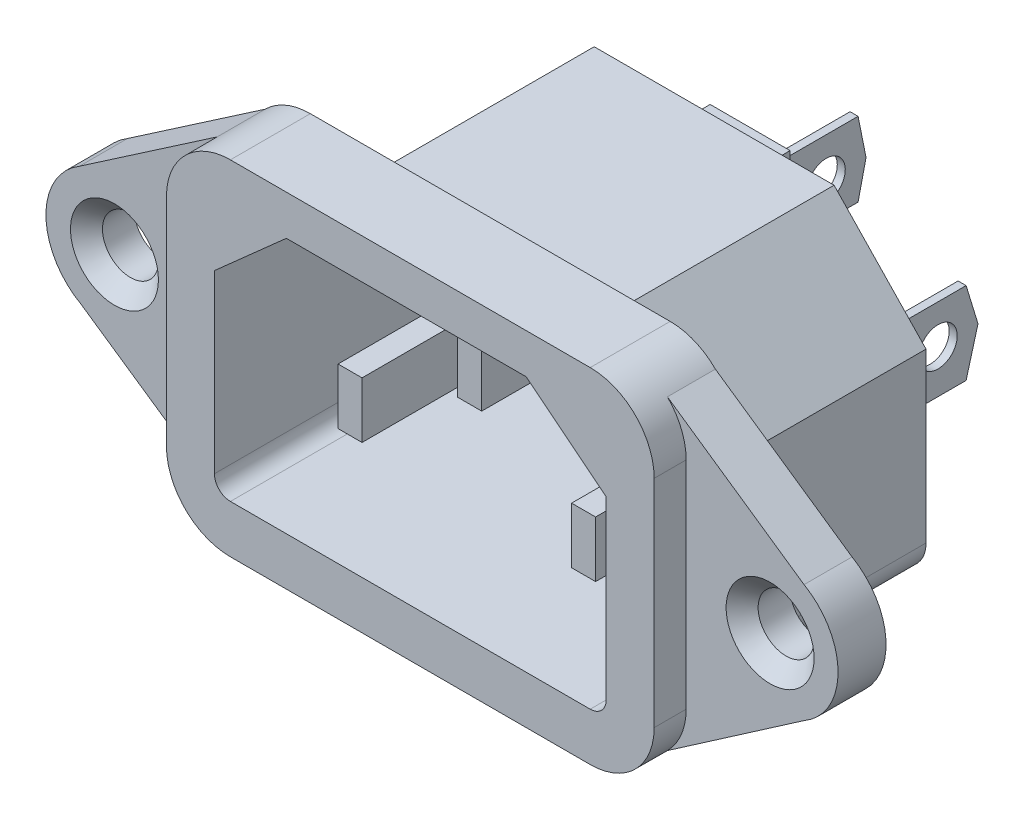
SolidWorks part; units mm, degrees
ref_plane "Спереди" through (0, 0, 0) normal (0, 0, 1) x (1, 0, 0)
ref_plane "Сверху" through (0, 0, 0) normal (0, 1, 0) x (1, 0, 0)
ref_plane "Справа" through (0, 0, 0) normal (1, 0, 0) x (0, 0, -1)
sketch "Эскиз1" plane through (0, 0, 0) normal (0, 0, 1) x (1, 0, 0)
  line L0 (23.0556, -0.5833) -> (-26.4444, -0.5833) construction
  line L1 (-12.9444, 10.1667) -> (9.5556, 10.1667)
  line L2 (-16.9444, 6.1667) -> (-16.9444, -7.3333)
  line L3 (-12.9444, -11.3333) -> (9.5556, -11.3333)
  line L4 (13.5556, 6.1667) -> (13.5556, -7.3333)
  line L5 (-15.7729, 8.9951) -> (-24.3879, 3.0982)
  line L6 (-24.2767, -4.329) -> (-15.7729, -10.1618)
  line L7 (12.384, 8.9951) -> (20.9289, 3.0982)
  line L8 (20.9289, -4.2649) -> (12.384, -10.1618)
  arc A0 (-12.9444, 10.1667) -> (-16.9444, 6.1667) centre (-12.9444, 6.1667) ccw
  arc A1 (-16.9444, -7.3333) -> (-12.9444, -11.3333) centre (-12.9444, -7.3333) ccw
  arc A2 (9.5556, -11.3333) -> (13.5556, -7.3333) centre (9.5556, -7.3333) ccw
  arc A3 (9.5556, 10.1667) -> (13.5556, 6.1667) centre (9.5556, 6.1667) cw
  circle A5 centre (-22.1944, -0.5833) radius 1.75
  circle A6 centre (18.8056, -0.5833) radius 1.75
  arc A7 (20.9289, -4.2649) -> (20.9289, 3.0982) centre (18.8056, -0.5833) ccw
  arc A8 (-24.3879, 3.0982) -> (-24.2767, -4.329) centre (-22.1944, -0.5833) ccw
  point P6 (-16.9444, 10.1667)
  point P11 (13.5556, -11.3333)
  point P14 (13.5556, 10.1667)
  point P21 (-16.9444, -0.5833)
  dimension "D3" = 4
  dimension "D5" = 4.25
  dimension "D6" = 4.25
  dimension "D1" = 30.5
  dimension "D2" = 21.5
  dimension "D4" = 9.5
  dimension "D7" = 5.25
  dimension "D8" = 5.25
extrude "Бобышка-Вытянуть1" add sketch "Эскиз1" against normal blind 3 contours L4 L0 L2 A1 L3 A2 | L0 L4 A3 L1 A0 L2 | A7 L0 A6 L4 A2 L8 | L0 A7 L7 A3 L4 A6 | L5 A8 L6 A1 L2 A5 A0 region at (17.0838, -3.9737, 0) region at (17.0838, 2.8071, 0) region at (-1.6944, -5.8625, 0) region at (-1.6944, 4.6958, 0) region at (-17.1639, -3.9583, 0)
sketch "Эскиз3" plane through (0, 0, 0) normal (0, 0, 1) x (1, 0, 0)
  line L0 (-12.9444, 10.1667) -> (9.5556, 10.1667) construction
  line L1 (-12.9444, 10.1667) -> (9.5556, 10.1667)
  line L2 (-16.9444, 6.1667) -> (-16.9444, -7.3333)
  line L3 (-12.9444, -11.3333) -> (9.5556, -11.3333)
  line L4 (13.5556, 6.1667) -> (13.5556, -7.3333)
  arc A0 (9.5556, 10.1667) -> (13.5556, 6.1667) centre (9.5556, 6.1667) cw
  arc A1 (9.5556, -11.3333) -> (13.5556, -7.3333) centre (9.5556, -7.3333) ccw
  arc A2 (-16.9444, -7.3333) -> (-12.9444, -11.3333) centre (-12.9444, -7.3333) ccw
  arc A3 (-12.9444, 10.1667) -> (-16.9444, 6.1667) centre (-12.9444, 6.1667) ccw
  point P4 (-1.6944, 10.1667)
  point P7 (-1.6944, 10.1667)
  point P10 (13.5556, 10.1667)
  point P15 (-16.9444, -11.3333)
  point P18 (-16.9444, 10.1667)
  dimension "D3" = 4
  dimension "D1" = 30.5
  dimension "D2" = 21.5
extrude "Бобышка-Вытянуть2" add sketch "Эскиз3" along normal blind 2
sketch "Эскиз4" plane through (0, 0, -3) normal (0, 0, -1) x (-1, 0, 0)
  line L0 (1.7119, 8.6668) -> (1.7119, -9.8333) construction
  line L1 (-5.8056, 8.6667) -> (9.1944, 8.6667)
  line L2 (-11.5556, 2.6667) -> (-11.5556, -7.8333)
  line L3 (-9.5556, -9.8333) -> (12.9795, -9.8333)
  line L4 (14.9795, 2.6667) -> (14.9795, -7.8333)
  line L5 (12.9444, 10.1667) -> (-9.5556, 10.1667) construction
  line L6 (12.9444, -11.3333) -> (-9.5556, -11.3333) construction
  line L7 (-11.2855, 2.6667) -> (-11.5556, 2.6667) construction
  line L11 (-11.5556, 2.6667) -> (-5.8056, 8.6667)
  line L12 (9.1944, 8.6667) -> (14.9795, 2.6667)
  arc A0 (-20.9289, 3.0982) -> (-20.9289, -4.2649) centre (-18.8056, -0.5833) ccw construction
  arc A1 (24.2767, -4.329) -> (24.3879, 3.0982) centre (22.1944, -0.5833) ccw construction
  arc A2 (-11.5556, -7.8333) -> (-9.5556, -9.8333) centre (-9.5556, -7.8333) ccw
  arc A3 (12.9795, -9.8333) -> (14.9795, -7.8333) centre (12.9795, -7.8333) ccw
  point P9 (-23.0556, -0.5833)
  point P12 (1.6944, 10.1667)
  point P17 (26.4795, -0.6475)
  point P19 (1.7119, 6.1202)
  dimension "D5" = 2
  dimension "D1" = 11.5
  dimension "D2" = 11.5
  dimension "D3" = 1.5
  dimension "D4" = 1.5
extrude "Бобышка-Вытянуть3" add sketch "Эскиз4" along normal blind 14
sketch "Эскиз5" plane through (0, 0, -3) normal (0, 0, -1) x (-1, 0, 0)
  line L0 (-17.1431, 3.368) -> (-10.047, 8.2024)
  line L1 (-10.047, 8.2024) -> (-8.1409, 8.2024)
  line L2 (-8.1409, 8.2024) -> (-13.1129, 2.8675)
  line L3 (-13.1129, 2.8675) -> (-13.1129, -7.3555)
  line L4 (-13.1129, -7.3555) -> (-17.1431, -4.5346)
  line L5 (20.5354, 3.368) -> (13.5142, 8.2024)
  line L6 (13.5142, 8.2024) -> (11.5035, 8.2024)
  line L7 (11.5035, 8.2024) -> (16.8383, 2.8675)
  line L8 (16.8383, 2.8675) -> (16.8383, -7.0285)
  line L9 (16.8383, -7.0285) -> (20.5354, -4.5346)
  arc A0 (-17.1431, -4.5346) -> (-17.1431, 3.368) centre (-18.8056, -0.5833) ccw
  arc A1 (20.5354, 3.368) -> (20.5354, -4.5346) centre (22.1944, -0.5833) ccw
extrude "Вырез-Вытянуть1" cut sketch "Эскиз5" against normal blind 1
chamfer "Фаска1" distance 1 angle 45 1 edges at (20.5556, -0.5833, 0)
chamfer "Фаска2" distance 1 angle 45 1 edges at (-20.4444, -0.5833, 0)
sketch "Эскиз6" plane through (0, 0, -17) normal (0, 0, -1) x (-1, 0, 0)
  line L0 (9.1944, 8.6667) -> (-5.8056, 8.6667) construction
  line L1 (-8.0556, 1.6667) -> (-3.0556, 1.6667)
  line L2 (-8.0556, 1.6667) -> (-8.0556, -8.3333)
  line L3 (-8.0556, -8.3333) -> (-3.0556, -8.3333)
  line L4 (-3.0556, 1.6667) -> (-3.0556, -8.3333)
  line L5 (-8.0556, 1.6667) -> (-3.0556, -8.3333) construction
  line L6 (-8.0556, -8.3333) -> (-3.0556, 1.6667) construction
  line L7 (-1.0556, 7.1667) -> (3.9444, 7.1667)
  line L8 (-1.0556, 7.1667) -> (-1.0556, -2.8333)
  line L9 (-1.0556, -2.8333) -> (3.9444, -2.8333)
  line L10 (3.9444, 7.1667) -> (3.9444, -2.8333)
  line L11 (-1.0556, 7.1667) -> (3.9444, -2.8333) construction
  line L12 (-1.0556, -2.8333) -> (3.9444, 7.1667) construction
  line L13 (6.4795, 1.6667) -> (11.4795, 1.6667)
  line L14 (6.4795, 1.6667) -> (6.4795, -8.3333)
  line L15 (6.4795, -8.3333) -> (11.4795, -8.3333)
  line L16 (11.4795, 1.6667) -> (11.4795, -8.3333)
  line L17 (6.4795, 1.6667) -> (11.4795, -8.3333) construction
  line L18 (6.4795, -8.3333) -> (11.4795, 1.6667) construction
  line L19 (9.1944, 8.6667) -> (-5.8056, 8.6667) construction
  line L20 (-11.5556, 2.6667) -> (-11.5556, -7.8333) construction
  line L21 (14.9795, -7.8333) -> (14.9795, 2.6667) construction
  line L22 (-9.5556, -9.8333) -> (12.9795, -9.8333) construction
  line L23 (-11.5556, 2.6667) -> (-11.5556, -7.8333) construction
  point P0 (-5.5556, -3.3333)
  point P5 (1.4444, 2.1667)
  point P10 (8.9795, -3.3333)
  dimension "D1" = 5
  dimension "D2" = 10
  dimension "D3" = 5
  dimension "D4" = 10
  dimension "D5" = 5
  dimension "D6" = 10
  dimension "D7" = 7
  dimension "D8" = 7
  dimension "D9" = 3.5
  dimension "D10" = 3.5
  dimension "D11" = 7
  dimension "D12" = 10.5
extrude "Бобышка-Вытянуть4" add sketch "Эскиз6" along normal blind 2
sketch "Эскиз7" plane through (0, 0, -19) normal (0, 0, -1) x (-1, 0, 0)
  line L0 (-8.0556, -8.3333) -> (-3.0556, -8.3333) construction
  line L1 (-5.8056, 0.6667) -> (-5.3056, 0.6667)
  line L2 (-5.8056, 0.6667) -> (-5.8056, -7.3333)
  line L3 (-5.8056, -7.3333) -> (-5.3056, -7.3333)
  line L4 (-5.3056, 0.6667) -> (-5.3056, -7.3333)
  line L5 (-8.0556, 1.6667) -> (-8.0556, -8.3333) construction
  line L7 (11.4795, -8.3333) -> (11.4795, 1.6667) construction
  line L8 (1.1944, 6.1667) -> (1.6944, 6.1667)
  line L9 (1.1944, 6.1667) -> (1.1944, -1.8333)
  line L10 (1.1944, -1.8333) -> (1.6944, -1.8333)
  line L11 (1.6944, 6.1667) -> (1.6944, -1.8333)
  line L12 (8.7295, 0.6667) -> (9.2295, 0.6667)
  line L13 (8.7295, 0.6667) -> (8.7295, -7.3333)
  line L14 (8.7295, -7.3333) -> (9.2295, -7.3333)
  line L15 (9.2295, 0.6667) -> (9.2295, -7.3333)
  line L16 (3.9444, -2.8333) -> (3.9444, 7.1667) construction
  line L17 (-1.0556, -2.8333) -> (3.9444, -2.8333) construction
  line L18 (6.4795, -8.3333) -> (11.4795, -8.3333) construction
  dimension "D1" = 0.5
  dimension "D2" = 8
  dimension "D3" = 1
  dimension "D4" = 2.25
  dimension "D5" = 0.5
  dimension "D6" = 8
  dimension "D7" = 0.5
  dimension "D8" = 8
  dimension "D9" = 2.25
  dimension "D10" = 2.25
  dimension "D11" = 1
  dimension "D12" = 1
extrude "Бобышка-Вытянуть5" add sketch "Эскиз7" along normal mid plane 14
sketch "Эскиз8" plane through (-9.2295, 0, 0) normal (-1, 0, 0) x (0, 0, 1)
  line L0 (-26, -3.3333) -> (-19, -3.3333) construction
  line L1 (-26, -3.3333) -> (-25.8529, -5.083)
  line L2 (-25.8529, -5.083) -> (-20.6676, -5.083)
  line L3 (-20.6676, -5.083) -> (-20.2818, -5.4689)
  line L4 (-19, -7.048) -> (-19, -7.3333)
  line L5 (-19, -7.3333) -> (-19, 0.6667) construction
  line L6 (-26, -7.3333) -> (-19, -7.3333) construction
  line L7 (-19, -7.3333) -> (-26, -7.3333)
  line L12 (-20.2818, -5.4689) -> (-19.1592, -5.4689)
  line L13 (-19.1592, -5.4689) -> (-20.0283, -7.1824)
  line L14 (-20.0283, -7.1824) -> (-19, -7.048)
  line L15 (-26, -7.3333) -> (-26, 0.6667)
  line L16 (-19, 0.6667) -> (-26, 0.6667)
  line L17 (-19, 0.3813) -> (-19, 0.6667)
  line L18 (-20.0283, 0.5157) -> (-19, 0.3813)
  line L19 (-19.1592, -1.1978) -> (-20.0283, 0.5157)
  line L20 (-20.2818, -1.1978) -> (-19.1592, -1.1978)
  line L21 (-20.6676, -1.5836) -> (-20.2818, -1.1978)
  line L22 (-25.8529, -1.5836) -> (-20.6676, -1.5836)
  line L23 (-26, -3.3333) -> (-25.8529, -1.5836)
  circle A0 centre (-23.4767, -3.3333) radius 1.2
  line M15 (-19, -7.3333) -> (-19, 0.6667)
  line M16 (-19, 0.6667) -> (-26, 0.6667)
  line M17 (-26, 0.6667) -> (-26, -7.3333)
  line M18 (-26, -7.3333) -> (-19, -7.3333)
extrude "Вырез-Вытянуть2" cut sketch "Эскиз8" against normal blind 3 contours L23 L22 L21 L20 L19 L18 M17 M15 M16 | L14 L13 L12 L3 L2 L1 M17 M18 M15 | A0 region at (-9.2295, -6.2115, -22.8481) region at (-9.2295, -0.4552, -22.8481)
sketch "Эскиз11" plane through (-1.6944, 0, 0) normal (-1, 0, 0) x (0, 0, 1)
  line L0 (-26, 2.1667) -> (-19, 2.1667) construction
  line L1 (-26, -1.8333) -> (-26, 6.1667) construction
  line L2 (-19, -1.8333) -> (-19, 6.1667) construction
  line L3 (-25.5002, 0) -> (-26, 2.1667)
  line L4 (-26, 6.1667) -> (-19, 6.1667)
  line L5 (-26, 6.1667) -> (-26, 4.6488)
  line L6 (-25.5002, 4.6488) -> (-19, 4.6488)
  line L7 (-19, 6.1667) -> (-19, 4.6488)
  line L8 (-26, -1.8333) -> (-19, -1.8333)
  line L9 (-26, -1.8333) -> (-26, 0)
  line L10 (-25.5002, 0) -> (-19, 0)
  line L11 (-19, -1.8333) -> (-19, 0)
  line L12 (-26, 2.1667) -> (-26, 0)
  line L13 (-26, 2.1667) -> (-25.5002, 4.6488)
  line L14 (-26, 2.1667) -> (-26, 4.6488)
  circle A0 centre (-23.5, 2.1667) radius 1.2
  line M14 (-19, -1.8333) -> (-19, 6.1667)
  line M15 (-19, 6.1667) -> (-26, 6.1667)
  line M16 (-26, 6.1667) -> (-26, -1.8333)
  line M17 (-26, -1.8333) -> (-19, -1.8333)
  dimension "D1" = 2.5
extrude "Вырез-Вытянуть3" cut sketch "Эскиз11" against normal blind 3 contours L0 A0 | A0 L0 | L13 L6 M16 M14 M15 | L10 L3 M16 M17 M14 region at (-1.6944, 1.6574, -23.5) region at (-1.6944, 2.676, -23.5) region at (-1.6944, -0.8503, -22.6349) region at (-1.6944, 5.3202, -22.6839)
sketch "Эскиз12" plane through (5.3056, 0, 0) normal (-1, 0, 0) x (0, 0, 1)
  line L0 (-26, -3.3333) -> (-19, -3.3333) construction
  line L1 (-26, -7.3333) -> (-26, 0.6667) construction
  line L2 (-19, -7.3333) -> (-19, 0.6667) construction
  line L3 (-25.2563, -6.0356) -> (-26, -3.3333)
  line L4 (-26, -7.3333) -> (-19, -7.3333)
  line L5 (-26, -7.3333) -> (-26, -6.0356)
  line L6 (-25.2563, -6.0356) -> (-19, -6.0356)
  line L7 (-19, -7.3333) -> (-19, -6.0356)
  line L8 (-26, 0.6667) -> (-19, 0.6667)
  line L9 (-26, 0.6667) -> (-26, -0.8964)
  line L10 (-25.2563, -0.8964) -> (-19, -0.8964)
  line L11 (-19, 0.6667) -> (-19, -0.8964)
  line L12 (-26, -3.3333) -> (-26, -6.0356)
  line L13 (-26, -3.3333) -> (-25.2563, -0.8964)
  line L14 (-26, -3.3333) -> (-26, -0.8964)
  circle A0 centre (-23.5, -3.3333) radius 1.2
  line M13 (-19, -7.3333) -> (-19, 0.6667)
  line M14 (-19, 0.6667) -> (-26, 0.6667)
  line M15 (-26, 0.6667) -> (-26, -7.3333)
  line M16 (-26, -7.3333) -> (-19, -7.3333)
  dimension "D1" = 2.5
extrude "Вырез-Вытянуть4" cut sketch "Эскиз12" against normal blind 3 contours L13 L10 M15 M13 M14 | L6 L3 M15 M16 M13 | L0 A0 | A0 L0 region at (5.3056, -3.8426, -23.5) region at (5.3056, -2.824, -23.5) region at (5.3056, -6.5301, -22.8239) region at (5.3056, -0.2368, -22.7487)
sketch "Эскиз15" plane through (0, 0, 2) normal (0, 0, 1) x (1, 0, 0)
  line L0 (9.5556, 10.1667) -> (-12.9444, 10.1667) construction
  line L1 (-9.4444, 7.6667) -> (5.5556, 7.6667)
  line L2 (-13.9444, 3.6667) -> (-13.9444, -7.3333)
  line L3 (-12.9444, -8.3333) -> (9.5556, -8.3333)
  line L4 (10.5556, 3.6667) -> (10.5556, -7.3333)
  line L5 (-16.9444, 6.1667) -> (-16.9444, -7.3333) construction
  line L10 (-1.6944, -8.3333) -> (-1.6944, 7.6667) construction
  line L14 (-9.4444, 7.6667) -> (-13.9444, 3.6667)
  line L15 (5.5556, 7.6667) -> (10.5556, 3.6667)
  arc A0 (9.5556, -8.3333) -> (10.5556, -7.3333) centre (9.5556, -7.3333) ccw
  arc A1 (-13.9444, -7.3333) -> (-12.9444, -8.3333) centre (-12.9444, -7.3333) ccw
  point P19 (-1.9444, 7.6667)
  point P20 (-1.6944, 6.231)
  point P21 (-1.6944, 6.231)
  dimension "D1" = 1
  dimension "D3" = 2.5
  dimension "D4" = 3
extrude "Вырез-Вытянуть6" cut sketch "Эскиз15" against normal blind 17
sketch "Эскиз16" plane through (0, 0, -19) normal (0, 0, -1) x (-1, 0, 0)
  line L0 (6.4795, 1.6667) -> (6.4795, -8.3333) construction
  line L1 (6.4795, -8.3333) -> (11.4795, -8.3333) construction
  line L2 (11.4795, -8.3333) -> (11.4795, 1.6667) construction
  line L3 (11.4795, 1.6667) -> (6.4795, 1.6667) construction
  line L4 (-1.0556, 7.1667) -> (-1.0556, -2.8333) construction
  line L5 (-1.0556, -2.8333) -> (3.9444, -2.8333) construction
  line L6 (3.9444, -2.8333) -> (3.9444, 7.1667) construction
  line L7 (3.9444, 7.1667) -> (-1.0556, 7.1667) construction
  line L8 (-8.0556, 1.6667) -> (-8.0556, -8.3333) construction
  line L9 (-8.0556, -8.3333) -> (-3.0556, -8.3333) construction
  line L10 (-3.0556, -8.3333) -> (-3.0556, 1.6667) construction
  line L11 (-3.0556, 1.6667) -> (-8.0556, 1.6667) construction
  line L12 (6.4795, 1.6667) -> (6.4795, -8.3333)
  line L13 (6.4795, -8.3333) -> (11.4795, -8.3333)
  line L14 (11.4795, -8.3333) -> (11.4795, 1.6667)
  line L15 (11.4795, 1.6667) -> (6.4795, 1.6667)
  line L16 (-1.0556, 7.1667) -> (-1.0556, -2.8333)
  line L17 (-1.0556, -2.8333) -> (3.9444, -2.8333)
  line L18 (3.9444, -2.8333) -> (3.9444, 7.1667)
  line L19 (3.9444, 7.1667) -> (-1.0556, 7.1667)
  line L20 (-8.0556, 1.6667) -> (-8.0556, -8.3333)
  line L21 (-8.0556, -8.3333) -> (-3.0556, -8.3333)
  line L22 (-3.0556, -8.3333) -> (-3.0556, 1.6667)
  line L23 (-3.0556, 1.6667) -> (-8.0556, 1.6667)
extrude "Бобышка-Вытянуть7" add sketch "Эскиз16" against normal blind 5
sketch "Эскиз17" plane through (0, 0, -14) normal (0, 0, 1) x (1, 0, 0)
  line L1 (-9.7114, -1.0234) -> (-8.2114, -1.0234)
  line L2 (-9.7114, -1.0234) -> (-9.7114, -4.5234)
  line L3 (-9.7114, -4.5234) -> (-8.2114, -4.5234)
  line L4 (-8.2114, -1.0234) -> (-8.2114, -4.5234)
  line L5 (-2.2287, 4.415) -> (-0.7287, 4.415)
  line L6 (-2.2287, 4.415) -> (-2.2287, 0.915)
  line L7 (-2.2287, 0.915) -> (-0.7287, 0.915)
  line L8 (-0.7287, 4.415) -> (-0.7287, 0.915)
  line L9 (4.892, -1.2569) -> (6.392, -1.2569)
  line L10 (4.892, -1.2569) -> (4.892, -4.7569)
  line L11 (4.892, -4.7569) -> (6.392, -4.7569)
  line L12 (6.392, -1.2569) -> (6.392, -4.7569)
  dimension "D1" = 1.5
  dimension "D2" = 3.5
  dimension "D3" = 1.5
  dimension "D4" = 3.5
  dimension "D5" = 1.5
  dimension "D6" = 3.5
extrude "Бобышка-Вытянуть8" add sketch "Эскиз17" along normal blind 12.5
sketch "Эскиз18" plane through (0, 0, -17) normal (0, 0, -1) x (-1, 0, 0)
  line L0 (-11.5556, 2.6667) -> (-11.5556, -9.8333) construction
